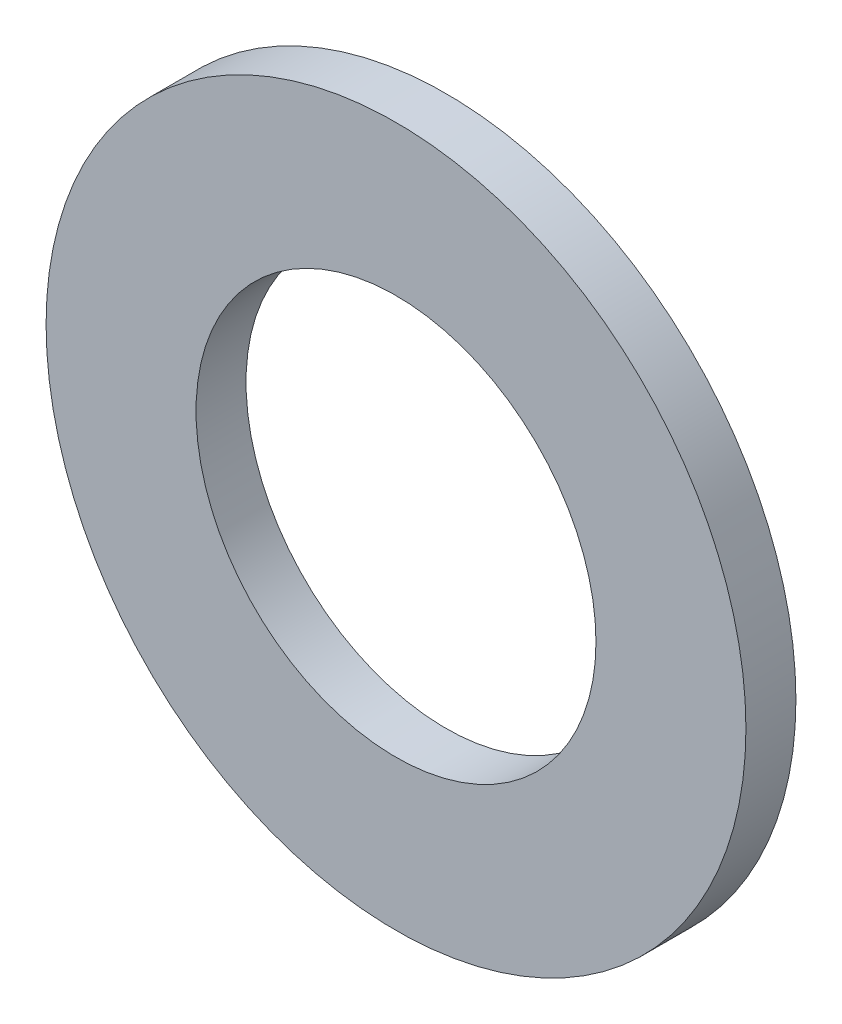
SolidWorks part; units mm, degrees
ref_plane "Спереди" through (0, 0, 0) normal (0, 0, 1) x (1, 0, 0)
ref_plane "Сверху" through (0, 0, 0) normal (0, 1, 0) x (1, 0, 0)
ref_plane "Справа" through (0, 0, 0) normal (1, 0, 0) x (0, 0, -1)
sketch "Эскиз1" plane through (0, 0, 0) normal (0, 0, 1) x (1, 0, 0)
  circle A0 centre (0, 0) radius 7
extrude "Вытянуть-Тонкостенный1" add sketch "Эскиз1" along normal blind 1 thin thin type one direction reverse wall 3
